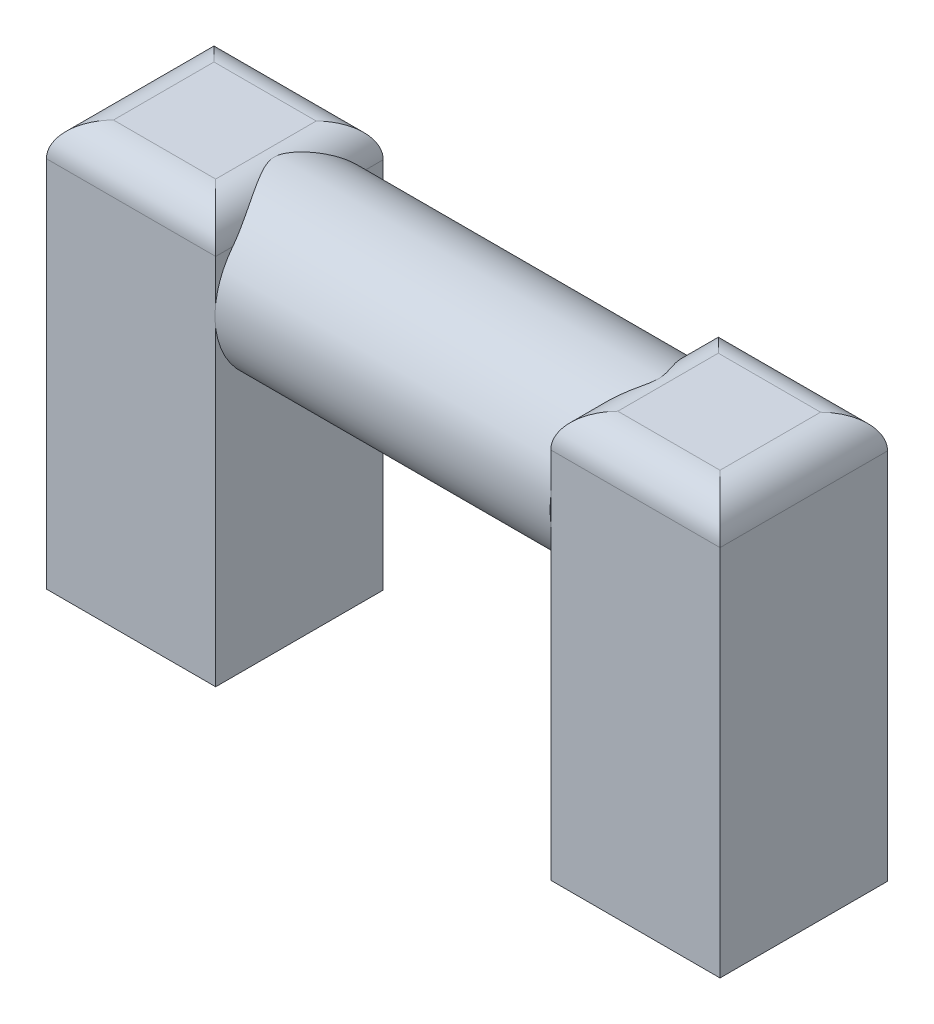
SolidWorks part; units mm, degrees
ref_plane "Ebene vorne" through (0, 0, 0) normal (0, 0, 1) x (1, 0, 0)
ref_plane "Ebene oben" through (0, 0, 0) normal (0, 1, 0) x (1, 0, 0)
ref_plane "Ebene rechts" through (0, 0, 0) normal (1, 0, 0) x (0, 0, -1)
sketch "Skizze1" plane through (0, 0, 0) normal (0, 0, 1) x (1, 0, 0)
  line L0 (0, 0) -> (-5.0514, 0)
  line L1 (-5.0514, 0) -> (-5.0514, 12.1233)
  line L2 (-5.0514, 12.1233) -> (0, 12.1233)
  line L3 (0, 12.1233) -> (0, 0)
  line L4 (10, 0) -> (15.0514, 0)
  line L5 (15.0514, 0) -> (15.0514, 12.1233)
  line L6 (15.0514, 12.1233) -> (10, 12.1233)
  line L7 (10, 12.1233) -> (10, 0)
  dimension "D1" = 10
extrude "Aufsatz-Linear austragen1" add sketch "Skizze1" along normal blind 5
sketch "Skizze2" plane through (0, 0, 0) normal (1, 0, 0) x (0, 0, -1)
  circle A0 centre (-2.5203, 9.5865) radius 2.5
  point P2 (-2.5203, 9.5865)
extrude "Aufsatz-Linear austragen2" add sketch "Skizze2" along normal blind 10
fillet "Verrundung4" radius 1 8 edges at (0, 12.1233, 2.5) (-2.5257, 12.1233, 5) (-5.0514, 12.1233, 2.5) (-2.5257, 12.1233, 0) (10, 12.1233, 2.5) (12.5257, 12.1233, 5) (15.0514, 12.1233, 2.5) (12.5257, 12.1233, 0)
